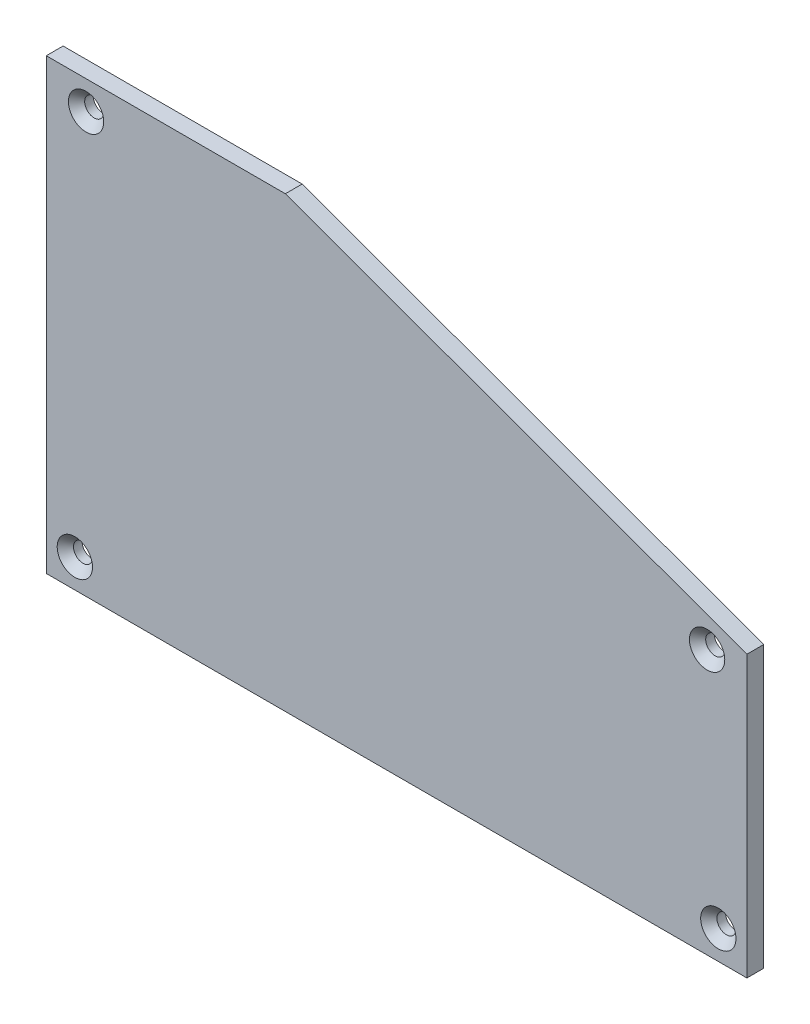
SolidWorks part; units mm, degrees
ref_plane "Спереди" through (0, 0, 0) normal (0, 0, 1) x (1, 0, 0)
ref_plane "Сверху" through (0, 0, 0) normal (0, 1, 0) x (1, 0, 0)
ref_plane "Справа" through (0, 0, 0) normal (1, 0, 0) x (0, 0, -1)
sketch "Эскиз1" plane through (0, 0, 0) normal (0, 0, 1) x (1, 0, 0)
  line L10 (-11.0949, 74) -> (71.25, 44.0289) construction
  line L11 (-53.75, 74) -> (-11.0949, 74) construction
  line L12 (-53.75, -6) -> (-53.75, 71) construction
  line L13 (71.25, -6) -> (-53.75, -6) construction
  line L14 (71.25, 41.9283) -> (71.25, -6) construction
  line L15 (-11.0949, 74) -> (71.25, 44.0289)
  line L16 (-53.75, 74) -> (-11.0949, 74)
  line L17 (-53.75, -6) -> (-53.75, 74)
  line L18 (71.25, -6) -> (-53.75, -6)
  line L19 (71.25, 44.0289) -> (71.25, -6)
  point P3 (0, 0)
  point P5 (71.25, 44.9283)
extrude "Бобышка-Вытянуть1" add sketch "Эскиз1" along normal blind 3
hole_wizard "Зенковка для винта с потайной головкой M31" positions "Эскиз4" profile "Эскиз5" countersink size "M3" standard "DIN" end condition through all
sketch "Эскиз4" plane through (0, 0, 3) normal (0, 0, 1) x (1, 0, 0)
  point P0 (-46.65, 68.9)
  point P3 (-48.65, -0.9)
  point P7 (64.15, 41.1858)
  point P10 (66.15, -0.9)
sketch "Эскиз5" plane through (-46.65, 68.9, 3) normal (1, 0, 0) x (0, -1, 0)
  line L0 (0, 0) -> (0, 3)
  line L1 (0, 3) -> (1.7, 3)
  line L2 (1.7, 3) -> (1.7, 1.45)
  line L3 (1.7, 1.45) -> (3.15, 0)
  line L5 (3.15, 0) -> (0, 0)
  line L6 (-1.7, 1.45) -> (-3.15, 0) construction
  line L11 (0, -6.35) -> (0, 107.95) construction
  dimension "Диаметр сквозного отверстия" = 3.4
  dimension "Глубина сквозного отверстия" = 3
  dimension "Диаметр передней зенковки" = 6.3
  dimension "Угол передней зенковки" = 90
